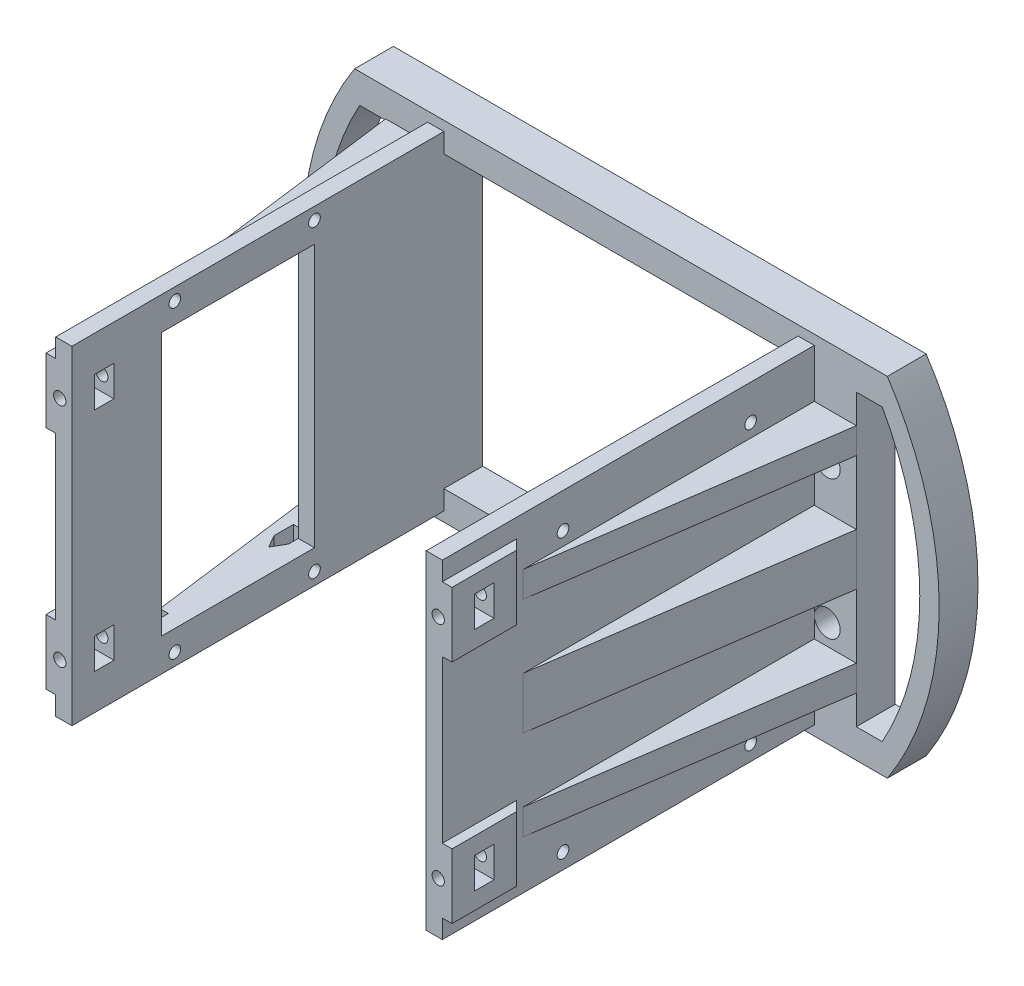
SolidWorks part; units mm, degrees
material "ABS"
ref_plane "Front Plane" through (0, 0, 0) normal (0, 0, 1) x (1, 0, 0)
ref_plane "Top Plane" through (0, 0, 0) normal (0, 1, 0) x (1, 0, 0)
ref_plane "Right Plane" through (0, 0, 0) normal (1, 0, 0) x (0, 0, -1)
sketch "Sketch1" plane through (0, 0, 0) normal (0, 0, 1) x (1, 0, 0)
  line L1 (-76.2, -50.8) -> (76.2, -50.8)
  line L2 (-76.2, -50.8) -> (-76.2, 50.8)
  line L3 (-76.2, 50.8) -> (76.2, 50.8)
  line L4 (76.2, -50.8) -> (76.2, 50.8)
  line L5 (-76.2, -50.8) -> (76.2, 50.8) construction
  line L6 (-76.2, 50.8) -> (76.2, -50.8) construction
  point P0 (0, 0)
  dimension "D1" = 152.4
  dimension "D2" = 101.6
extrude "Boss-Extrude1" add sketch "Sketch1" along normal blind 12
hole_wizard "#6 Clearance Hole1" positions "3DSketch1" profile "Sketch3" hole size "#6" standard "ANSI Inch" end condition through all
sketch3d "3DSketch1"
  line L1 (0, 21.4643, 12) -> (0, 21.4643, 0) construction
  line L2 (0, 21.4643, 0) -> (0, 0, 0) construction
  line L4 (0, 21.4643, 12) -> (0, -21.7157, 12) construction
  point P0 (-63.754, 21.4643, 12)
  point P4 (63.754, 21.4643, 12)
  point P6 (63.754, -21.7157, 12)
  point P8 (-63.754, -21.7157, 12)
  point P16 (0, 21.4643, 12)
  point P18 (0, -21.7157, 12)
  dimension "D1" = 43.18
  dimension "D2" = 21.4643
  dimension "D3" = 127.508
  dimension "D4" = 63.754
sketch "Sketch3" plane through (-63.754, 21.4643, 12) normal (1, 0, 0) x (0, -1, 0)
  line L0 (0, 0) -> (0, 12)
  line L1 (0, 12) -> (1.8986, 12)
  line L2 (1.8986, 12) -> (1.8986, 0)
  line L5 (1.8986, 0) -> (0, 0)
  line L11 (0, -6.35) -> (0, 107.95) construction
  dimension "Thru Hole Dia." = 3.7973
  dimension "Thru Hole Depth" = 12
sketch "Sketch4" plane through (0, 0, 12) normal (0, 0, 1) x (1, 0, 0)
  line L0 (-76.2, 50.8) -> (-84.2279, 50.8)
  line L1 (-76.2, -50.8) -> (-84.2279, -50.8)
  line L2 (76.2, -50.8) -> (84.2279, -50.8)
  line L3 (76.2, 50.8) -> (84.2279, 50.8)
  line L4 (0, 0) -> (0, 81.4816) construction
  line L5 (76.2, 50.8) -> (76.2, -50.8)
  line L6 (-76.2, 50.8) -> (-76.2, -50.8)
  arc A0 (-84.2279, 50.8) -> (-84.2279, -50.8) centre (0, 0) ccw
  arc A1 (84.2279, 50.8) -> (84.2279, -50.8) centre (0, 0) cw
  dimension "D1" = 98.3615
extrude "Boss-Extrude2" add sketch "Sketch4" against normal up to surface (12 mm away) up to face at (-61.8553, 21.4643, 0)
sketch "Sketch6" plane through (0, 0, 12) normal (0, 0, 1) x (1, 0, 0)
  line L37 (-63.754, -21.4643) -> (63.754, -21.4643) construction
  line L38 (-63.754, -21.4643) -> (-63.754, 21.4643) construction
  line L39 (-63.754, 21.4643) -> (63.754, 21.4643) construction
  line L40 (63.754, -21.4643) -> (63.754, 21.4643) construction
  line L41 (-63.754, -21.4643) -> (63.754, 21.4643) construction
  line L42 (-63.754, 21.4643) -> (63.754, -21.4643) construction
  circle A0 centre (-63.754, 21.4643) radius 4
  circle A1 centre (63.754, 21.4643) radius 4
  circle A2 centre (63.754, -21.4643) radius 4
  circle A3 centre (-63.754, -21.4643) radius 4
  point P0 (0, 0)
  dimension "D1" = 8
extrude "Cut-Extrude2" cut sketch "Sketch6" against normal blind 9.525
sketch "Sketch5" plane through (0, 0, 12) normal (0, 0, 1) x (1, 0, 0)
  line L4 (-72.754, 44.8) -> (-72.754, -44.8)
  line L5 (72.754, 44.8) -> (72.754, -44.8)
  line L6 (80.7688, 44.8) -> (-80.7688, 44.8)
  line L7 (-80.7688, -44.8) -> (80.7688, -44.8)
  line L8 (80.7688, 44.8) -> (72.754, 44.8)
  line L9 (-80.7688, -44.8) -> (-72.754, -44.8)
  line L10 (72.754, -44.8) -> (80.7688, -44.8)
  line L11 (-72.754, 44.8) -> (-80.7688, 44.8)
  line L12 (-63.754, 21.4643) -> (-63.754, -21.7157) construction
  line L14 (-54.754, 44.8) -> (-54.754, -44.8)
  line L19 (-54.754, 44.8) -> (54.754, 44.8)
  line L21 (-54.754, -44.8) -> (54.754, -44.8)
  line L22 (54.754, 44.8) -> (54.754, -44.8)
  line L23 (-54.754, 44.8) -> (54.754, -44.8) construction
  line L24 (-54.754, -44.8) -> (54.754, 44.8) construction
  line L25 (0, 21.4643) -> (0, -21.7157) construction
  arc A12 (80.7688, -44.8) -> (80.7688, 44.8) centre (0, 0) ccw
  arc A13 (-80.7688, 44.8) -> (-80.7688, -44.8) centre (0, 0) ccw
  arc A14 (80.7688, -44.8) -> (80.7688, 44.8) centre (0, 0) ccw
  arc A15 (-80.7688, 44.8) -> (-80.7688, -44.8) centre (0, 0) ccw
  point P5 (0, 5.467)
  point P8 (0, 0)
  point P9 (0, 0)
  point P12 (-53.4996, 44.8)
  point P18 (-53.6904, -44.8)
  dimension "D2" = 18
  dimension "D1" = 6
extrude "Cut-Extrude1" cut sketch "Sketch5" against normal through all
sketch "Sketch7" plane through (0, 0, 12) normal (0, 0, 1) x (1, 0, 0)
  line L1 (-59.754, 50.8) -> (-59.754, -50.8)
  line L5 (-54.754, 50.8) -> (-54.754, -50.8)
  line L6 (84.2279, 50.8) -> (-84.2279, 50.8) construction
  line L7 (-84.2279, -50.8) -> (84.2279, -50.8) construction
  line L8 (-54.754, 44.8) -> (-54.754, -44.8) construction
  line L9 (-54.754, -50.8) -> (-59.754, -50.8)
  line L10 (-54.754, 50.8) -> (-59.754, 50.8)
  circle A1 centre (-63.754, 21.4643) radius 4 construction
extrude "Boss-Extrude3" add sketch "Sketch7" along normal blind 100
hole_wizard "M3 Clearance Hole1" positions "3DSketch2" profile "Sketch8" hole size "M3" standard "ANSI Metric" end condition through all
sketch3d "3DSketch2"
  line L0 (-54.754, 46.99, 52) -> (-54.754, -46.99, 52) construction
  line L1 (-54.754, -46.99, 52) -> (-54.754, -46.99, 95.18) construction
  line L2 (-54.754, -46.99, 95.18) -> (-54.754, 46.99, 95.18) construction
  line L3 (-54.754, 46.99, 95.18) -> (-54.754, 46.99, 52) construction
  line L5 (-54.754, 0, 112) -> (-54.754, 0, 95.18) construction
  line L6 (-54.754, -50.8, 112) -> (-54.754, 50.8, 112) construction
  line L10 (-54.754, 44.8, 12) -> (-54.754, 50.8, 12) construction
  point P0 (-54.754, 46.99, 95.18)
  point P2 (-54.754, 46.99, 52)
  point P4 (-54.754, -46.99, 52)
  point P6 (-54.754, -46.99, 95.18)
  dimension "D1" = 93.98
  dimension "D2" = 43.18
  dimension "D3" = 40
sketch "Sketch8" plane through (-54.754, 46.99, 95.18) normal (0, 1, 0) x (0, 0, -1)
  line L0 (0, 0) -> (0, 43.6075)
  line L1 (0, 43.6075) -> (1.8, 43.6075)
  line L2 (1.8, 43.6075) -> (1.8, 0)
  line L5 (1.8, 0) -> (0, 0)
  line L11 (0, -6.35) -> (0, 107.95) construction
  dimension "Thru Hole Dia." = 3.6
  dimension "Thru Hole Depth" = 43.6075
sketch "Sketch9" plane through (-54.754, 0, 0) normal (1, 0, 0) x (0, 0, -1)
  line L6 (-52, -40.64) -> (-99.3, -40.64)
  line L7 (-99.3, -40.64) -> (-99.3, 40.64)
  line L8 (-99.3, 40.64) -> (-52, 40.64)
  line L9 (-52, 40.64) -> (-52, -40.64)
  line L10 (-12, -50.8) -> (-12, -44.8) construction
  line L11 (-112, -50.8) -> (-112, 50.8) construction
  line L12 (-112, -50.8) -> (-12, -50.8) construction
  line L13 (-112, 50.8) -> (-12, 50.8) construction
  dimension "D1" = 40
  dimension "D2" = 12.7
  dimension "D3" = 10.16
  dimension "D4" = 10.16
extrude "Cut-Extrude3" cut sketch "Sketch9" against normal through all
ref_plane "Plane1" through (-73.079, 0, 9.5003) normal (0.9917, 0, -0.1289) x (-0.1289, 0, -0.9917)
sketch "Sketch10" plane through (-73.079, 0, 9.5003) normal (0.9917, 0, -0.1289) x (-0.1289, 0, -0.9917)
  line L0 (-2.5208, -45.19) -> (-103.3622, -45.19)
  line L3 (-2.5208, -44.8) -> (-2.5208, 44.8) construction
  line L4 (-103.3622, 50.8) -> (-103.3622, -50.8) construction
  line L7 (-103.3622, -40.64) -> (-2.5208, -40.64)
  line L8 (-90.7682, -40.64) -> (-43.8629, -40.64) construction
  line L9 (-2.5208, -40.64) -> (-2.5208, -45.19)
  line L10 (-103.3622, -45.19) -> (-103.3622, -40.64)
  line L11 (61.6, 0) -> (-61.6, 0) construction
  line L20 (-2.5208, 45.19) -> (-103.3622, 45.19)
  line L24 (-2.5208, 40.64) -> (-2.5208, 45.19)
  line L25 (-103.3622, 40.64) -> (-2.5208, 40.64)
  line L26 (-103.3622, 45.19) -> (-103.3622, 40.64)
  ellipse E1 centre (-43.8629, -46.99) end of major axis (-43.8629, -45.19) minor radius 1.785 construction
  ellipse E3 centre (-43.8629, -46.99) end of major axis (-43.8629, -45.19) minor radius 1.785 construction
extrude "Boss-Extrude4" add sketch "Sketch10" along normal up to surface (13.1094 mm away) contours L10 L7 L9 L0 | L20 L26 L25 L24 up to face at (-59.754, 0, 75.65)
sketch "Sketch12" plane through (0, 0, 12) normal (0, 0, 1) x (1, 0, 0)
  line L9 (59.754, 50.8) -> (59.754, -50.8)
  line L10 (84.2279, 50.8) -> (-54.754, 50.8) construction
  line L11 (-54.754, -50.8) -> (84.2279, -50.8) construction
  line L12 (59.754, -50.8) -> (54.754, -50.8)
  line L13 (54.754, -50.8) -> (54.754, 50.8)
  line L14 (54.754, 50.8) -> (59.754, 50.8)
  line L15 (54.754, -44.8) -> (54.754, 44.8) construction
  circle A0 centre (63.754, 21.4643) radius 4 construction
sketch "Sketch25" plane through (0, -45.19, 0) normal (0, -1, 0) x (1, 0, 0)
  line L0 (-59.754, 52) -> (-64.254, 52) construction
  line L1 (-59.754, 95.18) -> (-61.9406, 95.18) construction
  line L2 (-62.3306, 92.18) -> (-59.754, 92.18)
  line L3 (-59.754, 49) -> (-64.254, 49)
  line L4 (-59.754, 49) -> (-59.754, 55)
  line L5 (-59.754, 55) -> (-64.254, 55) construction
  line L6 (-64.254, 49) -> (-64.254, 55)
  line L7 (-59.754, 49) -> (-64.254, 55) construction
  line L8 (-59.754, 55) -> (-64.254, 49) construction
  line L9 (-59.754, 92.18) -> (-59.754, 95.18)
  line L10 (-64.254, 55) -> (-62.004, 58.8971)
  line L11 (-62.004, 58.8971) -> (-59.754, 55)
  line L13 (-72.754, 12) -> (-59.754, 12)
  line L14 (-59.754, 12) -> (-59.754, 52)
  line L15 (-59.754, 52) -> (-59.754, 95.18)
  line L16 (-59.754, 95.18) -> (-59.754, 112)
  line L17 (-59.754, 112) -> (-72.754, 12)
  line L18 (-72.754, 12) -> (-59.754, 12)
  line L19 (-59.754, 49) -> (-59.754, 52)
  line L20 (-59.754, 52) -> (-59.754, 55)
  line L21 (-59.754, 95.18) -> (-59.754, 112)
  line L22 (-59.754, 112) -> (-62.3306, 92.18)
  point P6 (-62.004, 52)
  point P11 (0, 0)
  point P12 (-62.004, 55)
  line M13 (-59.754, 12) -> (-59.754, 52)
  line M14 (-59.754, 52) -> (-59.754, 95.18)
  line M15 (-59.754, 95.18) -> (-59.754, 112)
  line M16 (-59.754, 112) -> (-72.754, 12)
  dimension "D1" = 4.5
  dimension "D2" = 6
  dimension "D4" = 3
  dimension "D5" = 30
  dimension "D3" = 0
extrude "Cut-Extrude7" cut sketch "Sketch25" against normal through all both and the other way through all contours L2 M16 M14 M15 | L6 L3 L5 M13 M14 region at (-60.6129, -45.19, 98.7867) region at (-62.004, -45.19, 53.0539)
extrude "Boss-Extrude5" add sketch "Sketch12" along normal blind 90
hole_wizard "M3 Clearance Hole2" positions "3DSketch3" profile "Sketch13" hole size "M3" standard "ANSI Metric" end condition through all
sketch3d "3DSketch3"
  line L0 (54.754, 40, 31.68) -> (54.754, -46, 31.68) construction
  line L1 (54.754, -46, 31.68) -> (54.754, -46, 89.68) construction
  line L2 (54.754, -46, 89.68) -> (54.754, 40, 89.68) construction
  line L3 (54.754, 40, 89.68) -> (54.754, 40, 31.68) construction
  circle A0 centre (53.179, 40, 89.68) radius 1.375 construction
  circle A1 centre (53.179, 40, 31.68) radius 1.375 construction
  circle A2 centre (53.179, -46, 31.68) radius 1.375 construction
  point P0 (54.754, -46, 89.68)
  point P2 (54.754, -46, 31.68)
  point P4 (54.754, 40, 31.68)
  point P6 (54.754, 40, 89.68)
  point P25 (54.754, 43.3709, 88.4161)
  point P28 (51.804, 40, 89.68)
  point P29 (0, 0, 0)
  point P32 (51.804, 40, 31.68)
  point P33 (0, 0, 0)
  point P36 (51.804, -46, 31.68)
sketch "Sketch13" plane through (54.754, -46, 89.68) normal (0, 1, 0) x (0, 0, 1)
  line L0 (0, 0) -> (0, 43.6075)
  line L1 (0, 43.6075) -> (1.8, 43.6075)
  line L2 (1.8, 43.6075) -> (1.8, 0)
  line L5 (1.8, 0) -> (0, 0)
  line L11 (0, -6.35) -> (0, 107.95) construction
  dimension "Thru Hole Dia." = 3.6
  dimension "Thru Hole Depth" = 43.6075
ref_plane "Plane2" through (72.965, 0, 10.5394) normal (-0.9897, 0, -0.143) x (-0.143, 0, 0.9897)
sketch "Sketch14" plane through (72.965, 0, 10.5394) normal (-0.9897, 0, -0.143) x (-0.143, 0, 0.9897)
  line L0 (92.4098, -8) -> (1.4758, -8)
  line L1 (92.4098, -50.8) -> (92.4098, 50.8) construction
  line L2 (1.4758, 44.8) -> (1.4758, -44.8) construction
  line L3 (1.4758, -8) -> (1.4758, 8)
  line L4 (1.4758, 8) -> (92.4098, 8)
  line L5 (92.4098, 8) -> (92.4098, -8)
  line L6 (92.4098, 0) -> (1.4758, 0) construction
  line L8 (118.6772, -50.8) -> (19.7044, -50.8) construction
  line L9 (1.4758, -27.8) -> (92.4098, -27.8)
  line L10 (92.4098, -27.8) -> (92.4098, -35.8)
  line L11 (92.4098, -35.8) -> (1.4758, -35.8)
  line L12 (1.4758, -35.8) -> (1.4758, -27.8)
  line L14 (1.4758, 35.8) -> (1.4758, 27.8)
  line L15 (1.4758, 27.8) -> (92.4098, 27.8)
  line L16 (92.4098, 35.8) -> (1.4758, 35.8)
  line L17 (92.4098, 27.8) -> (92.4098, 35.8)
  point P12 (1.4758, 0)
  dimension "D1" = 16
  dimension "D2" = 15
  dimension "D3" = 8
extrude "Boss-Extrude6" add sketch "Sketch14" along normal up to surface (13.1349 mm away) contours L5 L0 L3 L4 | L12 L9 L10 L11 | L14 L15 L17 L16 up to face at (59.754, -47.8, 89.68)
sketch "Sketch15" plane through (0, 0, 102) normal (0, 0, 1) x (1, 0, 0)
  line L6 (59.754, -8) -> (59.754, 8)
  line L7 (59.754, -8) -> (59.754, 8)
  line L8 (59.754, 8) -> (59.754, 27.8)
  line L9 (59.754, 8) -> (59.754, 27.8)
  line L10 (59.754, 50.8) -> (54.754, 50.8)
  line L11 (54.754, 50.8) -> (54.754, -50.8)
  line L12 (54.754, -50.8) -> (59.754, -50.8)
  line L13 (59.754, -50.8) -> (59.754, -35.8)
  line L18 (59.754, -35.8) -> (59.754, -27.8)
  line L19 (59.754, -35.8) -> (59.754, -27.8)
  line L20 (59.754, 50.8) -> (54.754, 50.8)
  line L21 (54.754, 50.8) -> (54.754, -50.8)
  line L22 (54.754, -50.8) -> (59.754, -50.8)
  line L23 (59.754, -50.8) -> (59.754, -35.8)
  line L30 (59.754, -27.8) -> (59.754, -8)
  line L31 (59.754, -27.8) -> (59.754, -8)
  line L32 (59.754, 27.8) -> (59.754, 35.8)
  line L33 (59.754, 27.8) -> (59.754, 35.8)
  line L34 (59.754, 35.8) -> (59.754, 50.8)
  line L35 (59.754, 35.8) -> (59.754, 50.8)
  dimension "D1" = 0
extrude "Boss-Extrude7" add sketch "Sketch15" along normal blind 25
sketch "Sketch16" plane through (0, 0, 127) normal (0, 0, 1) x (1, 0, 0)
  line L4 (-54.754, 50.8) -> (-59.754, 50.8)
  line L5 (-59.754, 50.8) -> (-59.754, -50.8)
  line L6 (-59.754, -50.8) -> (-54.754, -50.8)
  line L7 (-54.754, -50.8) -> (-54.754, 50.8)
  line L8 (-54.754, 50.8) -> (-59.754, 50.8)
  line L9 (-59.754, 50.8) -> (-59.754, -50.8)
  line L10 (-59.754, -50.8) -> (-54.754, -50.8)
  line L11 (-54.754, -50.8) -> (-54.754, 50.8)
  dimension "D1" = 0
extrude "Boss-Extrude8" add sketch "Sketch16" against normal up to next
sketch "Sketch27" plane through (-59.754, 0, 0) normal (-1, 0, 0) x (0, 0, 1)
  line L3 (102, 45) -> (127, 45)
  line L5 (127, 50.8) -> (127, -50.8) construction
  line L6 (99.3, 0) -> (127, 0) construction
  line L7 (99.3, 40.64) -> (99.3, -40.64) construction
  line L8 (102, 45) -> (102, 25)
  line L9 (102, 25) -> (127, 25)
  line L10 (127, 25) -> (127, 45)
  line L12 (102, -25) -> (127, -25)
  line L13 (102, -45) -> (102, -25)
  line L14 (102, -45) -> (127, -45)
  line L15 (127, -25) -> (127, -45)
  point P12 (102, 35)
  dimension "D1" = 20
  dimension "D2" = 25
  dimension "D3" = 35
extrude "Boss-Extrude10" add sketch "Sketch27" along normal blind 3
chamfer "Chamfer1" distance 5 angle 45 2 edges at (-62.754, -35, 102) (-62.754, 35, 102)
mirror "Mirror1" about plane through (0, 0, 0) normal (1, 0, 0) of "Boss-Extrude10", "Chamfer1"
sketch "Sketch19" plane through (-59.754, 0, 0) normal (-1, 0, 0) x (0, 0, 1)
  line L0 (117, 50.8) -> (117, -50.8) construction
  line L1 (127, 50.8) -> (12, 50.8) construction
  line L2 (127, -50.8) -> (12, -50.8) construction
  line L3 (127, 50.8) -> (127, 45) construction
  line L4 (117, 0) -> (127, 0) construction
  line L5 (114, 30.2375) -> (120, 30.2375)
  line L6 (114, 30.2375) -> (114, 39.7625)
  line L7 (114, 39.7625) -> (120, 39.7625)
  line L8 (120, 30.2375) -> (120, 39.7625)
  line L9 (114, 30.2375) -> (120, 39.7625) construction
  line L10 (114, 39.7625) -> (120, 30.2375) construction
  line L11 (114, -39.7625) -> (120, -39.7625)
  line L12 (120, -30.2375) -> (120, -39.7625)
  line L13 (114, -30.2375) -> (120, -30.2375)
  line L14 (114, -30.2375) -> (114, -39.7625)
  line L15 (127, 25) -> (127, -25) construction
  point P16 (117, 35)
  point P19 (127, 0)
  dimension "D1" = 10
  dimension "D2" = 9.525
  dimension "D3" = 6
  dimension "D4" = 35
extrude "Cut-Extrude6" cut sketch "Sketch19" against normal through all both and the other way through all
sketch "Sketch20" plane through (0, 0, 0) normal (0, 0, -1) x (-1, 0, 0)
  line L0 (-82.3441, 53.8) -> (82.3441, 53.8)
  line L1 (-84.2279, 50.8) -> (84.2279, 50.8)
  line L2 (-98.3615, 0) -> (98.3615, 0) construction
  line L3 (-84.2279, -50.8) -> (84.2279, -50.8)
  line L4 (-82.3441, -53.8) -> (82.3441, -53.8)
  circle A0 centre (0, 0) radius 98.3615 construction
  arc A1 (84.2279, -50.8) -> (84.2279, 50.8) centre (0, 0) ccw construction
  arc A2 (-84.2279, 50.8) -> (-82.3441, 53.8) centre (0, 0) cw
  arc A3 (84.2279, 50.8) -> (82.3441, 53.8) centre (0, 0) ccw
  arc A4 (-84.2279, -50.8) -> (-82.3441, -53.8) centre (0, 0) ccw
  arc A5 (84.2279, -50.8) -> (82.3441, -53.8) centre (0, 0) cw
  dimension "D1" = 3
extrude "Boss-Extrude9" add sketch "Sketch20" against normal blind 12
sketch "Sketch22" plane through (0, 0, 127) normal (0, 0, 1) x (1, 0, 0)
  line L1 (-58.5, -35) -> (58.5, -35) construction
  line L2 (-58.5, -35) -> (-58.5, 35) construction
  line L3 (-58.5, 35) -> (58.5, 35) construction
  line L4 (58.5, -35) -> (58.5, 35) construction
  line L5 (-58.5, -35) -> (58.5, 35) construction
  line L6 (-58.5, 35) -> (58.5, -35) construction
  point P0 (0, 0)
  point P6 (0, 0)
  dimension "D1" = 35
  dimension "D2" = 117
hole_wizard "#6 Clearance Hole2" positions "3DSketch5" profile "Sketch24" hole size "#6" standard "ANSI Inch"
sketch3d "3DSketch5"
  point P0 (-58.5, 35, 127)
  point P3 (58.5, 35, 127)
  point P6 (58.5, -35, 127)
  point P9 (-58.5, -35, 127)
sketch "Sketch24" plane through (-58.5, 35, 127) normal (1, 0, 0) x (0, -1, 0)
  line L0 (0, 0) -> (0, 20)
  line L1 (0, 20) -> (1.8986, 18.8592)
  line L2 (1.8986, 18.8592) -> (1.8986, 0)
  line L5 (1.8986, 0) -> (0, 0)
  line L10 (0, 20) -> (-1.8987, 18.8592) construction
  line L11 (0, -6.35) -> (0, 107.95) construction
  dimension "Hole Dia." = 3.7973
  dimension "Hole Depth" = 20
  dimension "Drill Angle" = 118
